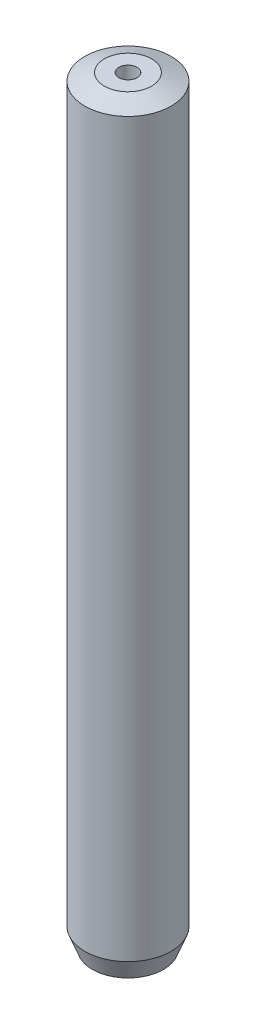
SolidWorks part; units mm, degrees
ref_plane "Front Plane" through (0, 0, 0) normal (0, 0, 1) x (1, 0, 0)
ref_plane "Top Plane" through (0, 0, 0) normal (0, 1, 0) x (1, 0, 0)
ref_plane "Right Plane" through (0, 0, 0) normal (1, 0, 0) x (0, 0, -1)
sketch "Sketch1" plane through (0, 0, 0) normal (0, 1, 0) x (1, 0, 0)
  circle A0 centre (0, 0) radius 5
  dimension "SHAFT_OD" = 10
extrude "Boss-Extrude1" add sketch "Sketch1" along normal blind 87.9561
sketch "Sketch2" plane through (0, 0, 0) normal (0, 1, 0) x (1, 0, 0)
  circle A0 centre (0, 0) radius 1.0505
  dimension "BORE_D" = 2.1009
extrude "Cut-Extrude1" cut sketch "Sketch2" along normal through all
chamfer "Chamfer1" distance 0.8771 angle 68.792 2 edges at (0, 87.9561, 5) (0, 0, 5) first distance on face at (0, 87.9561, 5) first distance on face at (0, 0, 1.0505)
